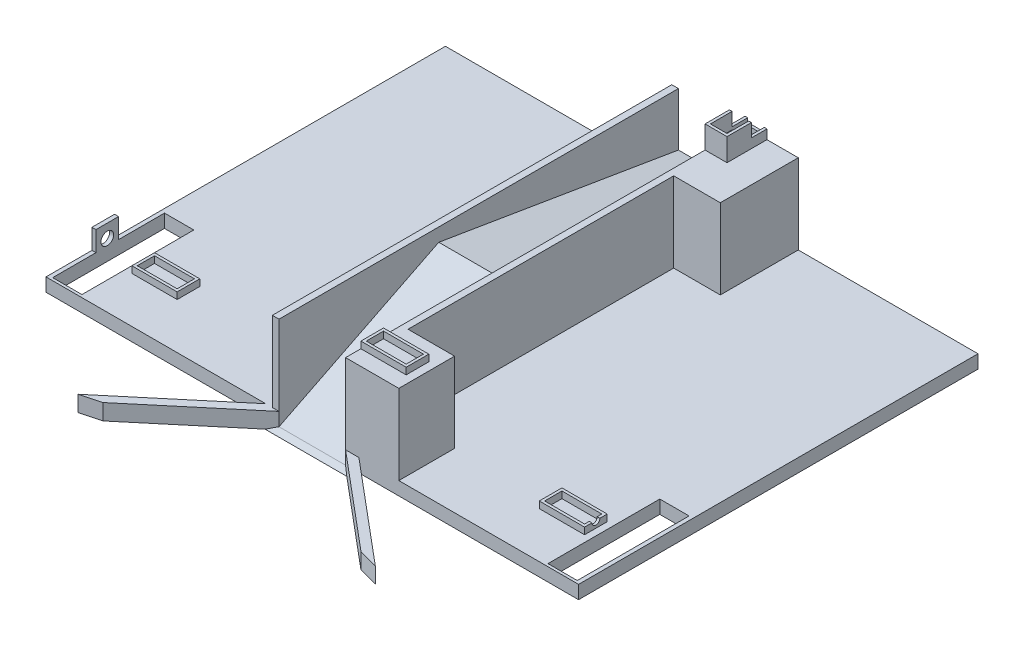
SolidWorks part; units mm, degrees
ref_plane "Front Plane" through (0, 0, 0) normal (0, 0, 1) x (1, 0, 0)
ref_plane "Top Plane" through (0, 0, 0) normal (0, 1, 0) x (1, 0, 0)
ref_plane "Right Plane" through (0, 0, 0) normal (1, 0, 0) x (0, 0, -1)
sketch "Sketch1" plane through (0, 0, 0) normal (0, 1, 0) x (1, 0, 0)
  line L1 (-117.9466, 258.1119) -> (282.0534, 258.1119)
  line L2 (-117.9466, 258.1119) -> (-117.9466, 44.1119)
  line L3 (-92.9466, -41.8881) -> (257.0534, -41.8881)
  line L5 (-117.9466, 44.1119) -> (-92.9466, 44.1119)
  line L8 (-92.9466, 44.1119) -> (-92.9466, -41.8881)
  line L23 (82.0534, 258.1119) -> (82.0534, -41.8881) construction
  line L32 (282.0534, 44.1119) -> (257.0534, 44.1119)
  line L33 (282.0534, 258.1119) -> (282.0534, 44.1119)
  line L34 (257.0534, 44.1119) -> (257.0534, -41.8881)
  point P1 (249.7959, 42.8761)
  point P2 (-103.5591, 44.0271)
  point P9 (-117.9466, 258.1119)
  point P32 (199.0884, -22.3492)
  dimension "D3" = 200
  dimension "D4" = 300
  dimension "D2" = 86
  dimension "D11" = 25
  dimension "D5" = 175
extrude "Boss-Extrude3" add sketch "Sketch1" along normal blind 10
sketch "Sketch2" plane through (0, 10, 0) normal (0, 1, 0) x (1, 0, 0)
  line L1 (-87.9466, 9.6119) -> (-53.9466, 9.6119)
  line L2 (-92.9466, 44.1119) -> (-92.9466, -41.8881) construction
  line L3 (-87.9466, 9.6119) -> (-87.9466, -7.3881)
  line L4 (-87.9466, -7.3881) -> (-53.9466, -7.3881)
  line L5 (-53.9466, 9.6119) -> (-53.9466, -7.3881)
  line L7 (-85.9466, 7.6119) -> (-55.9466, 7.6119)
  line L8 (-85.9466, 7.6119) -> (-85.9466, -5.3881)
  line L9 (-85.9466, -5.3881) -> (-55.9466, -5.3881)
  line L10 (-55.9466, 7.6119) -> (-55.9466, -5.3881)
  line L11 (-53.9466, 1.1119) -> (-87.9466, 1.1119) construction
  line L12 (-92.9466, -41.8881) -> (257.0534, -41.8881) construction
  line L13 (82.0534, 258.1119) -> (82.0534, -41.8881) construction
  line L14 (282.0534, 258.1119) -> (-117.9466, 258.1119) construction
  line L15 (218.0534, 1.1119) -> (252.0534, 1.1119) construction
  line L17 (220.0534, 7.6119) -> (220.0534, -5.3881)
  line L18 (250.0534, -5.3881) -> (220.0534, -5.3881)
  line L19 (250.0534, 7.6119) -> (250.0534, -5.3881)
  line L20 (250.0534, 7.6119) -> (220.0534, 7.6119)
  line L21 (218.0534, 9.6119) -> (218.0534, -7.3881)
  line L22 (252.0534, -7.3881) -> (218.0534, -7.3881)
  line L23 (252.0534, 9.6119) -> (252.0534, -7.3881)
  line L24 (252.0534, 9.6119) -> (218.0534, 9.6119)
  point P13 (0, 0)
  point P33 (0, 0)
  point P34 (0, 0)
  dimension "D1" = 2
  dimension "D3" = 2
  dimension "D4" = 2
  dimension "D5" = 30
  dimension "D6" = 13
  dimension "D7" = 43
  dimension "D2" = 2
  dimension "D8" = 5
extrude "Boss-Extrude4" add sketch "Sketch2" along normal blind 5
sketch "Sketch3" plane through (0, 10, 0) normal (0, 1, 0) x (1, 0, 0)
  line L0 (82.0534, 258.1119) -> (82.0534, -41.8881) construction
  line L1 (282.0534, 258.1119) -> (-117.9466, 258.1119) construction
  line L2 (-92.9466, -41.8881) -> (257.0534, -41.8881) construction
  line L3 (57.0534, -41.8881) -> (57.0534, 78.1119)
  line L4 (57.0534, 78.1119) -> (107.0534, 78.1119)
  line L5 (107.0534, 78.1119) -> (107.0534, -41.8881)
  line L24 (257.0534, -41.8881) -> (257.0534, 44.1119)
  line L25 (257.0534, 44.1119) -> (282.0534, 44.1119)
  line L26 (282.0534, 44.1119) -> (282.0534, 258.1119)
  line L27 (282.0534, 258.1119) -> (-117.9466, 258.1119)
  line L28 (-117.9466, 258.1119) -> (-117.9466, 44.1119)
  line L29 (-117.9466, 44.1119) -> (-92.9466, 44.1119)
  line L30 (-92.9466, 44.1119) -> (-92.9466, -41.8881)
  line L35 (-92.9466, -41.8881) -> (257.0534, -41.8881)
  line L51 (57.0534, -41.8881) -> (107.0534, -41.8881)
  dimension "D1" = 50
  dimension "D2" = 25
  dimension "D3" = 120
extrude "Boss-Extrude5" add sketch "Sketch3" along normal blind 50
sketch "Sketch4" plane through (107.0534, 0, 0) normal (1, 0, 0) x (0, 0, -1)
  line L2 (-41.8881, 60) -> (78.1119, 60)
  line L3 (78.1119, 60) -> (-41.8881, 0)
  line L4 (-41.8881, 60) -> (-41.8881, 0)
extrude "Cut-Extrude2" cut sketch "Sketch4" against normal up to vertex (50 mm away) up to point (57.0534, 60, 41.8881)
sketch "Sketch5" plane through (0, 10, 0) normal (0, 1, 0) x (1, 0, 0)
  line L0 (57.0534, 78.1119) -> (57.0534, 258.1119)
  line L1 (282.0534, 258.1119) -> (-117.9466, 258.1119) construction
  line L2 (57.0534, 258.1119) -> (107.0534, 258.1119)
  line L3 (107.0534, 258.1119) -> (107.0534, 78.1119)
  line L4 (57.0534, 78.1119) -> (107.0534, 78.1119)
  line L5 (57.0534, 78.1119) -> (57.0534, -21.8881) construction
extrude "Boss-Extrude6" add sketch "Sketch5" along normal blind 50
sketch "Sketch6" plane through (107.0534, 0, 0) normal (1, 0, 0) x (0, 0, -1)
  line L2 (78.1119, 60) -> (258.1119, 60)
  line L3 (258.1119, 60) -> (258.1119, 30)
  line L4 (258.1119, 60) -> (258.1119, 10) construction
  line L5 (258.1119, 30) -> (78.1119, 60)
  dimension "D1" = 30
extrude "Cut-Extrude3" cut sketch "Sketch6" against normal through all contours L2 L3 L5
sketch "Sketch7" plane through (0, 0, 0) normal (0, 1, 0) x (1, 0, 0)
  line L0 (52.0534, 258.1119) -> (52.0534, -41.8881)
  line L1 (57.0534, 258.1119) -> (-117.9466, 258.1119) construction
  line L2 (-92.9466, -41.8881) -> (57.0534, -41.8881) construction
  line L3 (52.0534, -41.8881) -> (57.0534, -41.8881)
  line L4 (57.0534, -41.8881) -> (57.0534, 258.1119)
  line L5 (57.0534, 258.1119) -> (57.0534, -21.8881) construction
  line L6 (57.0534, 258.1119) -> (107.0534, 258.1119) construction
  line L7 (57.0534, 258.1119) -> (52.0534, 258.1119)
  line L8 (107.0534, 258.1119) -> (112.0534, 258.1119)
  line L9 (282.0534, 258.1119) -> (107.0534, 258.1119) construction
  line L10 (112.0534, 258.1119) -> (112.0534, -41.8881)
  line L11 (107.0534, -41.8881) -> (257.0534, -41.8881) construction
  line L12 (112.0534, -41.8881) -> (107.0534, -41.8881)
  line L13 (107.0534, -41.8881) -> (107.0534, 258.1119)
  line L14 (112.0534, -41.8881) -> (147.0534, -41.8881)
  line L15 (107.0534, -41.8881) -> (257.0534, -41.8881) construction
  line L16 (147.0534, -41.8881) -> (147.0534, 0)
  line L17 (147.0534, 0) -> (112.0534, 0)
  dimension "D1" = 5
  dimension "D2" = 5
  dimension "D3" = 35
extrude "Boss-Extrude7" add sketch "Sketch7" along normal blind 70 contours L16 L17 L10 L14 | L7 L0 L3 L4 | L13 L8 L10 L12 region at (129.5534, 0, 20.9441)
sketch "Sketch9" plane through (0, 70, 0) normal (0, 1, 0) x (1, 0, 0)
  line L0 (107.0534, -41.8881) -> (107.0534, 78.1119) construction
  line L1 (107.0534, -13.3881) -> (141.0534, -13.3881)
  line L2 (107.0534, -13.3881) -> (107.0534, -30.3881)
  line L3 (107.0534, -30.3881) -> (141.0534, -30.3881)
  line L4 (141.0534, -13.3881) -> (141.0534, -30.3881)
  line L5 (141.0534, -21.8881) -> (107.0534, -21.8881) construction
  line L6 (109.0534, -15.3881) -> (139.0534, -15.3881)
  line L7 (109.0534, -15.3881) -> (109.0534, -28.3881)
  line L8 (109.0534, -28.3881) -> (139.0534, -28.3881)
  line L9 (139.0534, -15.3881) -> (139.0534, -28.3881)
  line L10 (124.0534, -13.3881) -> (124.0534, -35.4954) construction
  line L11 (147.0534, -41.8881) -> (107.0534, -41.8881) construction
  dimension "D1" = 2
  dimension "D2" = 2
  dimension "D3" = 2
  dimension "D4" = 2
  dimension "D5" = 30
  dimension "D6" = 13
  dimension "D7" = 20
extrude "Boss-Extrude8" add sketch "Sketch9" along normal blind 5 contours L2 L1 L4 L3 | L7 L6 L9 L8
sketch "Sketch10" plane through (112.0534, 0, 0) normal (1, 0, 0) x (0, 0, -1)
  line L0 (199.5615, 70) -> (199.5615, 10)
  line L1 (258.1119, 70) -> (0, 70) construction
  line L2 (0, 10) -> (258.1119, 10) construction
  line L3 (199.5615, 10) -> (258.1119, 10)
  line L4 (258.1119, 10) -> (258.1119, 70)
  line L5 (258.1119, 70) -> (199.5615, 70)
extrude "Boss-Extrude9" add sketch "Sketch10" along normal blind 35
sketch "Sketch13" plane through (0, 70, 0) normal (0, 1, 0) x (1, 0, 0)
  line L0 (123.5534, 228.1119) -> (107.0534, 228.1119)
  line L2 (107.0534, 228.1119) -> (107.0534, 258.1119)
  line L3 (107.0534, 258.1119) -> (123.5534, 258.1119)
  line L4 (123.5534, 258.1119) -> (123.5534, 228.1119)
  line L5 (121.5534, 230.1119) -> (109.0534, 230.1119)
  line L6 (109.0534, 230.1119) -> (109.0534, 256.1119)
  line L7 (109.0534, 256.1119) -> (121.5534, 256.1119)
  line L8 (121.5534, 256.1119) -> (121.5534, 230.1119)
  line L15 (107.0534, 258.1119) -> (147.0534, 258.1119) construction
  dimension "D2" = 16.5
  dimension "D3" = 30
  dimension "D4" = 2
  dimension "D5" = 2
  dimension "D6" = 2
  dimension "D7" = 2
extrude "Boss-Extrude11" add sketch "Sketch13" along normal blind 7
sketch "Sketch14" plane through (0, 0, 0) normal (0, -1, 0) x (1, 0, 0)
  line L0 (282.0534, -44.1119) -> (282.0534, -258.1119) construction
  line L1 (282.0534, -258.1119) -> (-117.9466, -258.1119) construction
  circle A0 centre (267.0534, -243.1119) radius 8
  dimension "D1" = 15
  dimension "D2" = 15
sketch "Sketch16" plane through (0, 0, 0) normal (0, -1, 0) x (1, 0, 0)
  line L0 (-117.9466, -258.1119) -> (-117.9466, -44.1119) construction
  line L1 (282.0534, -258.1119) -> (-117.9466, -258.1119) construction
  circle A0 centre (-102.9466, -243.1119) radius 8
  dimension "D1" = 15
  dimension "D2" = 15
sketch "Sketch19" plane through (0, 0, 41.8881) normal (0, 0, 1) x (1, 0, 0)
  line L0 (-92.9466, 10) -> (52.0534, 10) construction
  line L1 (57.0534, 0) -> (47.0534, 0)
  line L2 (57.0534, 0) -> (57.0534, 10)
  line L3 (57.0534, 10) -> (47.0534, 10)
  line L4 (47.0534, 0) -> (47.0534, 10)
  line L6 (107.0534, 0) -> (117.0534, 0)
  line L7 (107.0534, 0) -> (107.0534, 10)
  line L8 (107.0534, 10) -> (117.0534, 10)
  line L9 (117.0534, 0) -> (117.0534, 10)
  point P12 (0, 0)
  point P13 (0, 0)
  dimension "D1" = 10
  dimension "D2" = 10
  dimension "D3" = 10
sketch "Sketch20" plane through (0, 0, 0) normal (0, 1, 0) x (1, 0, 0)
  line L0 (47.0534, -41.8881) -> (-29.551, -106.1669)
  line L2 (57.0534, -41.8881) -> (-14.8596, -102.2304)
  line L4 (-92.9466, -41.8881) -> (52.0534, -41.8881) construction
  line L5 (107.0534, -41.8881) -> (178.9665, -102.2304)
  line L6 (117.0534, -41.8881) -> (193.6579, -106.1669)
  line L7 (107.0534, -41.8881) -> (117.0534, -41.8881) construction
  line L8 (147.0534, -41.8881) -> (107.0534, -41.8881) construction
  line L9 (178.9665, -102.2304) -> (193.6579, -106.1669)
  line L10 (-14.8596, -102.2304) -> (-29.551, -106.1669)
  line L11 (47.0534, -41.8881) -> (57.0534, -41.8881)
  line L12 (107.0534, -41.8881) -> (117.0534, -41.8881)
  point P2 (0, 0)
  point P3 (0, 0)
  point P6 (0, 0)
  point P7 (0, 0)
  point P19 (0, 0)
  point P20 (0, 0)
  point P21 (0, 0)
  point P22 (0, 0)
  point P24 (0, 0)
  point P34 (0, 0)
  point P35 (0, 0)
  dimension "D1" = 40
  dimension "D2" = 40
  dimension "D3" = 25
  dimension "D4" = 25
  dimension "D5" = 100
  dimension "D6" = 100
  dimension "D7" = 10
  dimension "D8" = 10
extrude "Boss-Extrude16" add sketch "Sketch20" along normal blind 10 and the other way blind 2
sketch "Sketch21" plane through (0, 0, 0) normal (0, -1, 0) x (1, 0, 0)
  line L1 (57.0534, 41.8881) -> (107.0534, 41.8881)
  line L2 (57.0534, 31.8881) -> (57.0534, 11.8881)
  line L3 (57.0534, 11.8881) -> (107.0534, 11.8881)
  line L4 (107.0534, 31.8881) -> (107.0534, 11.8881)
  line L5 (47.0534, 41.8881) -> (47.0534, 31.8881)
  line L6 (47.0534, 31.8881) -> (57.0534, 31.8881)
  line L7 (117.0534, 41.8881) -> (117.0534, 31.8881)
  line L8 (107.0534, 41.8881) -> (117.0534, 41.8881) construction
  line L9 (117.0534, 31.8881) -> (107.0534, 31.8881)
  line L10 (47.0534, 41.8881) -> (57.0534, 41.8881)
  line L11 (107.0534, 41.8881) -> (117.0534, 41.8881)
  point P14 (0, 0)
  dimension "D1" = 50
  dimension "D2" = 30
  dimension "D3" = 10
  dimension "D4" = 10
extrude "Boss-Extrude19" add sketch "Sketch21" along normal blind 2
sketch "Sketch23" plane through (107.0534, 0, 0) normal (1, 0, 0) x (0, 0, -1)
  line L4 (-41.8881, 0) -> (-46.6881, -2)
  line L5 (-102.2304, -2) -> (-41.8881, -2) construction
  line L6 (-46.6881, -2) -> (-41.8881, -2)
  line L7 (-41.8881, -2) -> (-41.8881, 0) construction
  line L8 (-41.8881, 0) -> (-41.8881, -2)
  dimension "D1" = 22.62
extrude "Boss-Extrude23" add sketch "Sketch23" against normal up to surface and the other way up to surface separate body contours L8 L6 L4 up to face at (28.2882, 3.2, 66.025) other way up to face at (135.8187, 3.2, 66.025)
sketch "Sketch28" plane through (0, 0, -44.1119) normal (0, 0, 1) x (1, 0, 0)
  line L0 (-117.9466, 0) -> (-92.9466, 0) construction
  line L1 (-117.9466, 10) -> (-114.9466, 10)
  line L2 (-117.9466, 10) -> (-117.9466, 0)
  line L3 (-117.9466, 0) -> (-114.9466, 0)
  line L4 (-114.9466, 10) -> (-114.9466, 0)
  dimension "D1" = 3
extrude "Boss-Extrude24" add sketch "Sketch28" along normal up to vertex (86 mm away) up to point (-92.9466, 0, 41.8881)
sketch "Sketch30" plane through (0, 0, -44.1119) normal (0, 0, 1) x (1, 0, 0)
  line L0 (257.0534, 0) -> (282.0534, 0) construction
  line L1 (282.0534, 10) -> (279.0534, 10)
  line L2 (282.0534, 10) -> (282.0534, 0)
  line L3 (282.0534, 0) -> (279.0534, 0)
  line L4 (279.0534, 10) -> (279.0534, 0)
  dimension "D1" = 3
extrude "Boss-Extrude26" add sketch "Sketch30" along normal up to vertex (86 mm away) up to point (257.0534, 0, 41.8881)
sketch "Sketch32" plane through (0, 70, 0) normal (0, 1, 0) x (1, 0, 0)
  line L0 (109.0534, 256.1119) -> (109.0534, 230.1119) construction
  line L1 (121.5534, 230.1119) -> (109.0534, 230.1119)
  line L2 (121.5534, 230.1119) -> (121.5534, 246.4119)
  line L3 (121.5534, 246.4119) -> (109.0534, 246.4119)
  line L4 (109.0534, 230.1119) -> (109.0534, 246.4119)
  dimension "D1" = 16.3
extrude "Boss-Extrude28" add sketch "Sketch32" along normal blind 5
sketch "Sketch34" plane through (0, 77, 0) normal (0, 1, 0) x (1, 0, 0)
  line L0 (109.0534, 246.4119) -> (107.0534, 246.4119)
  line L1 (107.0534, 258.1119) -> (107.0534, 228.1119) construction
  line L2 (107.0534, 246.4119) -> (107.0534, 228.1119)
  line L3 (107.0534, 228.1119) -> (123.5534, 228.1119)
  line L4 (107.0534, 228.1119) -> (123.5534, 228.1119) construction
  line L5 (123.5534, 228.1119) -> (123.5534, 246.4119)
  line L6 (123.5534, 228.1119) -> (123.5534, 258.1119) construction
  line L7 (123.5534, 246.4119) -> (121.5534, 246.4119)
  line L8 (121.5534, 246.4119) -> (121.5534, 230.1119)
  line L9 (121.5534, 230.1119) -> (109.0534, 230.1119)
  line L10 (109.0534, 230.1119) -> (109.0534, 246.4119)
extrude "Boss-Extrude31" add sketch "Sketch34" along normal blind 10
sketch "Sketch35" plane through (0, 0, -258.1119) normal (0, 0, -1) x (-1, 0, 0)
  line L0 (-121.5534, 77) -> (-121.5534, 74)
  line L1 (-123.5534, 77) -> (-107.0534, 77) construction
  line L2 (-121.5534, 74) -> (-109.0534, 74)
  line L3 (-109.0534, 74) -> (-109.0534, 77)
  line L4 (-123.5534, 77) -> (-123.5534, 70) construction
  line L5 (-107.0534, 77) -> (-107.0534, 30) construction
  line L6 (-121.5534, 77) -> (-109.0534, 77)
  dimension "D1" = 2
  dimension "D2" = 2
  dimension "D3" = 3
extrude "Cut-Extrude4" cut sketch "Sketch35" against normal up to next (2 mm away)
sketch "Sketch47" plane through (252.0534, 0, 0) normal (1, 0, 0) x (0, 0, -1)
  line L0 (-7.3881, 15) -> (9.6119, 15) construction
  line L1 (-1.8881, 15) -> (4.1119, 15)
  arc A0 (4.1119, 15) -> (-1.8881, 15) centre (1.1119, 15) cw
  dimension "D1" = 3
extrude "Cut-Extrude14" cut sketch "Sketch47" against normal up to next (2 mm away)
sketch "Sketch41" plane through (0, 10, 0) normal (0, 1, 0) x (1, 0, 0)
  line L0 (-117.9466, 9.6119) -> (-114.9466, 9.6119)
  line L1 (-117.9466, -41.8881) -> (-117.9466, 258.1119) construction
  line L2 (-114.9466, -41.8881) -> (-114.9466, 44.1119) construction
  line L3 (-114.9466, 9.6119) -> (-114.9466, -7.3881)
  line L4 (-114.9466, -7.3881) -> (-117.9466, -7.3881)
  line L5 (-117.9466, -7.3881) -> (-117.9466, 9.6119)
  line L6 (-117.9466, 9.6119) -> (-87.9466, 9.6119) construction
  line L7 (-117.9466, -7.3881) -> (-87.9466, -7.3881) construction
extrude "Boss-Extrude33" add sketch "Sketch41" along normal blind 15
sketch "Sketch42" plane through (-117.9466, 0, 0) normal (-1, 0, 0) x (0, 0, 1)
  line L0 (-9.6119, 25) -> (-9.6119, 10) construction
  line L3 (-9.6119, 15) -> (7.3881, 15) construction
  line L4 (7.3881, 25) -> (7.3881, 10) construction
  line L5 (41.8881, 10) -> (-258.1119, 10) construction
  circle A0 centre (-1.1119, 15) radius 4.75
  point P0 (-9.6119, 15)
  dimension "D2" = 9.5
  dimension "D1" = 5
extrude "Cut-Extrude11" cut sketch "Sketch42" against normal up to next (3 mm away)
extrude "Boss-Extrude34" add sketch "Sketch14" along normal blind 5
extrude "Boss-Extrude35" add sketch "Sketch16" along normal blind 5
sketch "Sketch43" plane through (-92.9466, 0, 0) normal (-1, 0, 0) x (0, 0, 1)
  line L0 (-44.1119, 0) -> (41.8881, 0) construction
  line L1 (41.8881, 10) -> (39.8881, 10)
  line L2 (41.8881, 10) -> (41.8881, 0)
  line L3 (41.8881, 0) -> (39.8881, 0)
  line L4 (39.8881, 10) -> (39.8881, 0)
  dimension "D1" = 2
extrude "Boss-Extrude36" add sketch "Sketch43" along normal up to next (22 mm away)
sketch "Sketch44" plane through (257.0534, 0, 0) normal (1, 0, 0) x (0, 0, -1)
  line L0 (-41.8881, 0) -> (44.1119, 0) construction
  line L1 (-41.8881, 10) -> (-39.8881, 10)
  line L2 (-41.8881, 10) -> (-41.8881, 0)
  line L3 (-41.8881, 0) -> (-39.8881, 0)
  line L4 (-39.8881, 10) -> (-39.8881, 0)
  dimension "D1" = 2
extrude "Boss-Extrude37" add sketch "Sketch44" along normal up to next
equation "\"draggingScrewDiameter\"= 2"
equation "\"chassisWidth\"= 400"
equation "\"D3@Sketch1\"=0.5 * \"chassisWidth\""
equation "\"chassisLength\"=300"
equation "\"D4@Sketch1\"=\"chassisLength\""
equation "\"wheelDepth\"= 86"
equation "\"D2@Sketch1\"=\"wheelDepth\""
equation "\"wheelWidth\"= 25"
equation "\"baseThickness\"=10"
equation "\"D1@Boss-Extrude3\"=\"baseThickness\""
equation "\"D7@Sketch2\"=\"wheelDepth\" * 0.5"
equation "\"rampLength\"=120"
equation "\"D3@Sketch3\"=\"rampLength\""
equation "\"rampHeight\"=50"
equation "\"D1@Boss-Extrude5\"=\"rampHeight\""
equation "\"D1@Boss-Extrude6\"=\"rampHeight\""
equation "\"dumpHeight\"=30"
equation "\"D1@Sketch6\"=\"dumpHeight\""
equation "\"D11@Sketch1\"=\"wheelWidth\""
equation "\"D5@Sketch1\"=(0.5 * \"chassisWidth\") - \"wheelWidth\""
equation "\"D1@Sketch23\"=atn(\"rampHeight\"/\"rampLength\")"
